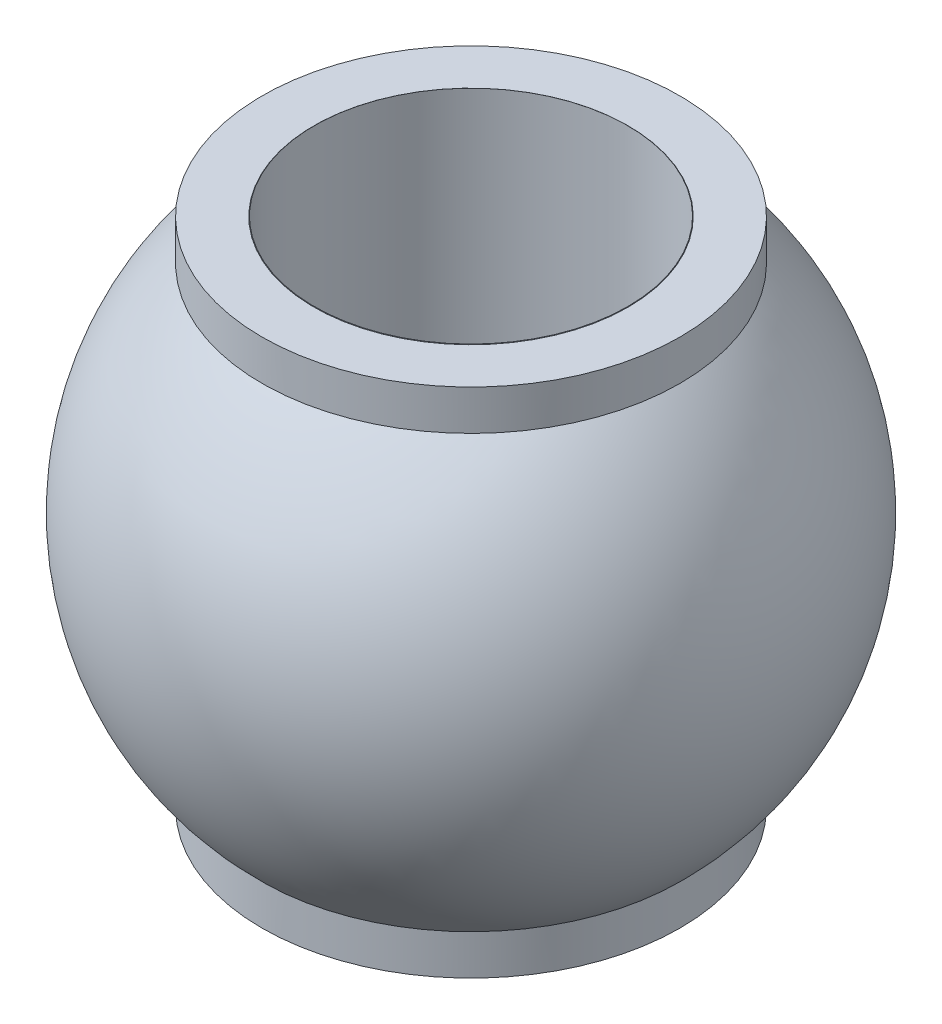
SolidWorks part; units mm, degrees
ref_plane "Front Plane" through (0, 0, 0) normal (0, 0, 1) x (1, 0, 0)
ref_plane "Top Plane" through (0, 0, 0) normal (0, 1, 0) x (1, 0, 0)
ref_plane "Right Plane" through (0, 0, 0) normal (1, 0, 0) x (0, 0, -1)
ref_axis "Axis1" through (0, 55, 0) along (0, -1, 0)
sketch "Sketch1" plane through (0, 0, 0) normal (0, 0, 1) x (1, 0, 0)
  line L1 (0, -2.875) -> (0, 2.875)
  arc A0 (0, 2.875) -> (0, -2.875) centre (0, 0) ccw
  dimension "D1" = 5.75
revolve "Revolve1" add sketch "Sketch1" angle 360 about axis through (0, 55, 0) along (0, -1, 0)
sketch "Sketch2" plane through (0, 0, 0) normal (0, 1, 0) x (1, 0, 0)
  circle A0 centre (0, 0) radius 2
  circle A1 centre (0, 0) radius 1.5
  dimension "D1" = 4
  dimension "D2" = 3
extrude "Boss-Extrude1" add sketch "Sketch2" along normal mid plane 4.9
shell "Shell1" [suppressed] thickness 0.4
extrude "Cut-Extrude1" cut sketch "Sketch2<3>" against normal mid plane 6 contours A1 region at (0, 0, 0)
sketch "Sketch2<3>" plane through (0, 0, 0) normal (0, 1, 0) x (1, 0, 0) same geometry as "Sketch2"
